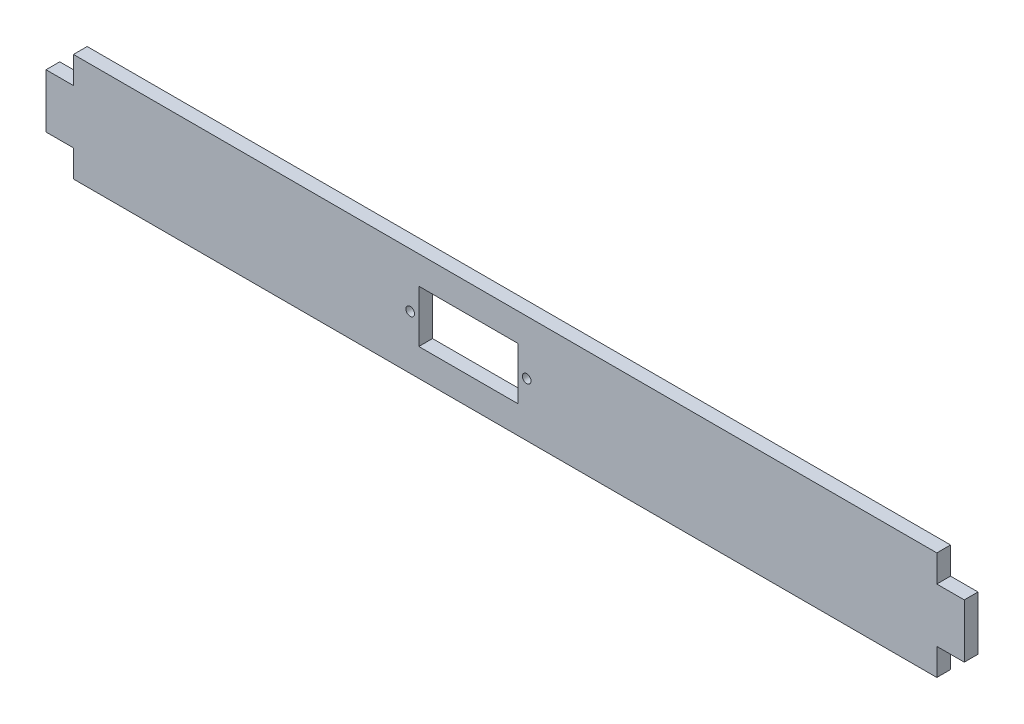
SolidWorks part; units mm, degrees
ref_plane "Front Plane" through (0, 0, 0) normal (0, 0, 1) x (1, 0, 0)
ref_plane "Top Plane" through (0, 0, 0) normal (0, 1, 0) x (1, 0, 0)
ref_plane "Right Plane" through (0, 0, 0) normal (1, 0, 0) x (0, 0, -1)
sketch "Sketch2" plane through (0, 0, 0) normal (0, 0, 1) x (1, 0, 0)
  line L1 (0, 0) -> (200, 0)
  line L2 (0, 0) -> (0, 25)
  line L3 (0, 25) -> (200, 25)
  line L4 (200, 0) -> (200, 25)
  dimension "D1" = 200
  dimension "D2" = 25
extrude "Boss-Extrude1" add sketch "Sketch2" along normal mid plane 3.18
sketch "Sketch4" plane through (0, 0, -1.59) normal (0, 0, -1) x (-1, 0, 0)
  line L0 (-91.5, 18.5075) -> (-91.5, 6.4075) construction
  line L1 (-103, 18.5075) -> (-80, 18.5075)
  line L2 (-103, 18.5075) -> (-103, 6.4075)
  line L3 (-103, 6.4075) -> (-80, 6.4075)
  line L4 (-80, 18.5075) -> (-80, 6.4075)
  line L5 (0, 25) -> (0, 0) construction
  circle A2 centre (-105, 12.4575) radius 1
  circle A3 centre (-78, 12.4575) radius 1
  dimension "D3" = 2
  dimension "D4" = 2
  dimension "D1" = 23
  dimension "D2" = 12.1
  dimension "D5" = 80
extrude "Cut-Extrude1" cut sketch "Sketch4" against normal blind 3.18
sketch "Sketch5" plane through (0, 0, -1.59) normal (0, 0, -1) x (-1, 0, 0)
  line L5 (-200, 0) -> (-200, 25) construction
  line L6 (-200, 18.75) -> (-206.36, 18.75)
  line L7 (-200, 18.75) -> (-200, 6.25)
  line L8 (-200, 6.25) -> (-206.36, 6.25)
  line L9 (-206.36, 18.75) -> (-206.36, 6.25)
  line L10 (0, 0) -> (-200, 0) construction
  line L11 (-100, 25) -> (-100, 0) construction
  line L12 (-200, 25) -> (0, 25) construction
  line L13 (0, 12.5) -> (-200, 12.5) construction
  line L14 (0, 25) -> (0, 0) construction
  line L15 (0, 6.25) -> (6.36, 6.25)
  line L16 (6.36, 18.75) -> (6.36, 6.25)
  line L17 (0, 18.75) -> (6.36, 18.75)
  line L18 (0, 18.75) -> (0, 6.25)
  dimension "D1" = 12.5
  dimension "D2" = 6.36
extrude "Boss-Extrude2" add sketch "Sketch5" against normal blind 3.18
equation "\"Acrylic Sheet Thickness\"= 3.18mm"
equation "\"D1@Sketch5\"=25/2"
